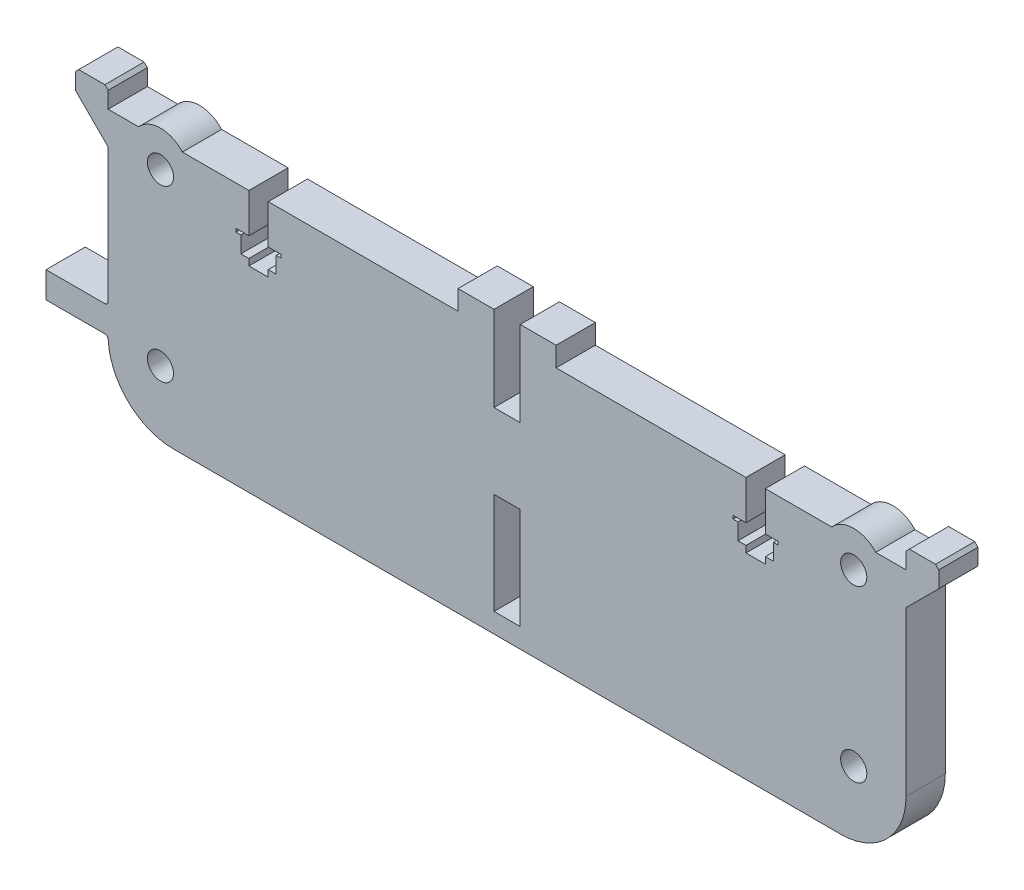
SolidWorks part; units mm, degrees
material "Oak"
ref_plane "Front Plane" through (0, 0, 0) normal (0, 0, 1) x (1, 0, 0)
ref_plane "Top Plane" through (0, 0, 0) normal (0, 1, 0) x (1, 0, 0)
ref_plane "Right Plane" through (0, 0, 0) normal (1, 0, 0) x (0, 0, -1)
sketch "Sketch1" plane through (0, 0, 0) normal (0, 0, 1) x (1, 0, 0)
  line L0 (0, -43.0686) -> (0, 56.6488) construction
  line L1 (-7.5, 17) -> (-49.6459, 17)
  line L2 (49, 8) -> (65, 8) construction
  line L3 (49, 8) -> (49, -8) construction
  line L4 (49, -8) -> (65, -8) construction
  line L5 (65, 8) -> (65, -8) construction
  line L6 (61, 17) -> (61, 20)
  line L7 (61, 20) -> (66, 20)
  line L8 (66, 20) -> (66, 17)
  line L9 (-7.5, 17) -> (-7.5, 20)
  line L10 (61, -23) -> (0, -23)
  line L11 (49, 8) -> (65, -8) construction
  line L12 (65, 8) -> (49, -8) construction
  line L13 (-65, 8) -> (-49, -8) construction
  line L14 (-49, 8) -> (-65, -8) construction
  line L15 (-65, 8) -> (-65, -8) construction
  line L16 (-49, -8) -> (-65, -8) construction
  line L17 (-49, 8) -> (-49, -8) construction
  line L18 (-49, 8) -> (-65, 8) construction
  line L19 (-7.5, 20) -> (-2, 20)
  line L20 (-66, 20) -> (-66, 17)
  line L21 (-61, 20) -> (-66, 20)
  line L22 (-61, 17) -> (-61, 20)
  line L23 (7.5, 17) -> (7.5, 20)
  line L24 (7.5, 20) -> (2, 20)
  line L25 (7.5, 17) -> (49.6459, 17)
  line L26 (-56.3541, 17) -> (-61, 17)
  line L27 (2, 20) -> (2, 7)
  line L28 (-57, 0) -> (57, 0) construction
  line L29 (2, 7) -> (-2, 7)
  line L30 (2, -20) -> (2, -4.5)
  line L31 (2, -4.5) -> (-2, -4.5)
  line L32 (56.3541, 17) -> (61, 17)
  line L33 (0, -23) -> (-61, -23)
  line L34 (-2, -20) -> (-2, -4.5)
  line L35 (-2, 20) -> (-2, 7)
  line L40 (-2, -20) -> (2, -20)
  line L43 (-61, -23) -> (-61, 12)
  line L44 (-61, 12) -> (-66, 17)
  line L45 (61, -23) -> (61, 12)
  line L46 (61, 12) -> (66, 17)
  arc A0 (-49.6459, 17) -> (-56.3541, 17) centre (-53, 14) ccw
  arc A1 (56.3541, 17) -> (49.6459, 17) centre (53, 14) ccw
  point P7 (-57, 0)
  point P9 (57, 0)
  point P20 (0, 0)
  point P24 (0, 40)
  point P27 (73.331, 42)
  point P30 (0, 40)
  point P31 (68.331, 17)
  point P32 (99.8, 42)
  point P38 (98.8347, 49.7973)
  point P52 (0, -4.5)
  point P54 (0, 7)
  dimension "D8" = 4.5
  dimension "D1" = 16
  dimension "D2" = 65
  dimension "D3" = 61
  dimension "D4" = 5
  dimension "D5" = 15
  dimension "D6" = 53
  dimension "D7" = 53
  dimension "D10" = 3
  dimension "D11" = 11.5
  dimension "D12" = 17
  dimension "D13" = 4
  dimension "D14" = 122
  dimension "D9" = 3
  dimension "D15" = 14
  dimension "D16" = 40
extrude "Boss-Extrude1" add sketch "Sketch1" along normal blind 6
sketch "Sketch2" plane through (0, 0, 6) normal (0, 0, 1) x (1, 0, 0)
  line L0 (0, 0) -> (0, -23) construction
  line L5 (-61, -23) -> (61, -23) construction
  line L7 (45, -6) -> (45, 10) construction
  line L8 (45, -6) -> (61, -6) construction
  line L9 (45, 10) -> (61, 10) construction
  line L10 (61, -6) -> (61, 10) construction
  line L11 (45, -6) -> (61, 10) construction
  line L12 (45, 10) -> (61, -6) construction
  line L13 (49.6459, 17) -> (7.5, 17) construction
  circle A0 centre (53, -13) radius 2
  circle A1 centre (53, 13) radius 2
  point P7 (53, 2)
  dimension "D2" = 4
  dimension "D1" = 53
  dimension "D4" = 15
  dimension "D6" = 15
  dimension "D7" = 16
  dimension "D16" = 11
extrude "Cut-Extrude1" cut sketch "Sketch2" against normal through all
mirror "Mirror1" about plane through (0, 0, 0) normal (1, 0, 0) of "Cut-Extrude1"
chamfer "Chamfer1" distance 0.5 angle 45 4 edges at (66, 20, 3) (61, 20, 3) (-61, 20, 3) (-66, 20, 3)
fillet "Fillet1" radius 10 2 edges at (61, -23, 3) (-61, -23, 3)
sketch "Sketch3" plane through (0, 0, 6) normal (0, 0, 1) x (1, 0, 0)
  line L0 (-61, 12) -> (-61, -13) construction
  line L1 (-57.0317, -9) -> (-70.5, -9)
  line L2 (-57.0317, -9) -> (-57.0317, -13)
  line L3 (-57.0317, -13) -> (-70.5, -13)
  line L4 (-70.5, -9) -> (-70.5, -13)
  line L5 (-51, -23) -> (51, -23) construction
  dimension "D1" = 9.5
  dimension "D2" = 10
  dimension "D3" = 4
extrude "Boss-Extrude3" add sketch "Sketch3" against normal through all
sketch "Sketch4" plane through (0, 0, 6) normal (0, 0, 1) x (1, 0, 0)
  line L0 (0, 0) -> (0, 22.5154) construction
  line L1 (-38, 17) -> (-38, 7) construction
  line L2 (-7.5, 17) -> (-49.6459, 17) construction
  line L3 (-39.48, 17) -> (-39.48, 11)
  line L4 (-39.48, 11) -> (-41.45, 11)
  line L5 (-41.45, 11) -> (-41.45, 10.5)
  line L6 (-41.45, 10.5) -> (-40.7, 10.5)
  line L7 (-40.7, 10.5) -> (-40.7, 8)
  line L8 (-40.7, 8) -> (-39.48, 8)
  line L9 (-39.48, 8) -> (-39.48, 7)
  line L10 (-39.48, 7) -> (-36.52, 7)
  line L11 (-36.52, 8) -> (-36.52, 7)
  line L12 (-35.3, 8) -> (-36.52, 8)
  line L13 (-35.3, 10.5) -> (-35.3, 8)
  line L14 (-34.55, 10.5) -> (-35.3, 10.5)
  line L15 (-34.55, 11) -> (-34.55, 10.5)
  line L16 (-36.52, 11) -> (-34.55, 11)
  line L17 (-36.52, 17) -> (-36.52, 11)
  line L18 (38, 17) -> (38, 7) construction
  line L19 (36.52, 17) -> (36.52, 11)
  line L20 (36.52, 11) -> (34.55, 11)
  line L21 (34.55, 11) -> (34.55, 10.5)
  line L22 (34.55, 10.5) -> (35.3, 10.5)
  line L23 (35.3, 10.5) -> (35.3, 8)
  line L24 (35.3, 8) -> (36.52, 8)
  line L25 (36.52, 8) -> (36.52, 7)
  line L26 (39.48, 7) -> (36.52, 7)
  line L27 (39.48, 8) -> (39.48, 7)
  line L28 (40.7, 8) -> (39.48, 8)
  line L29 (40.7, 10.5) -> (40.7, 8)
  line L30 (41.45, 10.5) -> (40.7, 10.5)
  line L31 (41.45, 11) -> (41.45, 10.5)
  line L32 (39.48, 11) -> (41.45, 11)
  line L33 (39.48, 17) -> (39.48, 11)
  line L34 (-39.48, 17) -> (-36.52, 17)
  line L35 (36.52, 17) -> (39.48, 17)
  dimension "D1" = 0.5
  dimension "D2" = 2.5
  dimension "D3" = 1
  dimension "D4" = 10
  dimension "D5" = 2.96
  dimension "D6" = 6.9
  dimension "D7" = 5.4
  dimension "D8" = 38
extrude "Cut-Extrude2" cut sketch "Sketch4" against normal through all
fillet "Fillet2" radius 0.5 2 edges at (-61, -13, 3) (-61, -9, 3)
equation "\"bed-plate-thickness\"=3"
equation "\"D1@Boss-Extrude1\"=\"y-rib-thickness\""
equation "\"D10@Sketch1\"=\"bed-plate-thickness\""
equation "\"D13@Sketch1\"=\"y-cross-rib-thickness\""
equation "\"y-cross-rib-thickness\"=4"
equation "\"y-rib-thickness\"=6"
equation "\"x-plate-thickness\"=5"
equation "\"rod-diameter\"=12"
equation "\"t-nut-hole-diameter\"=3"
